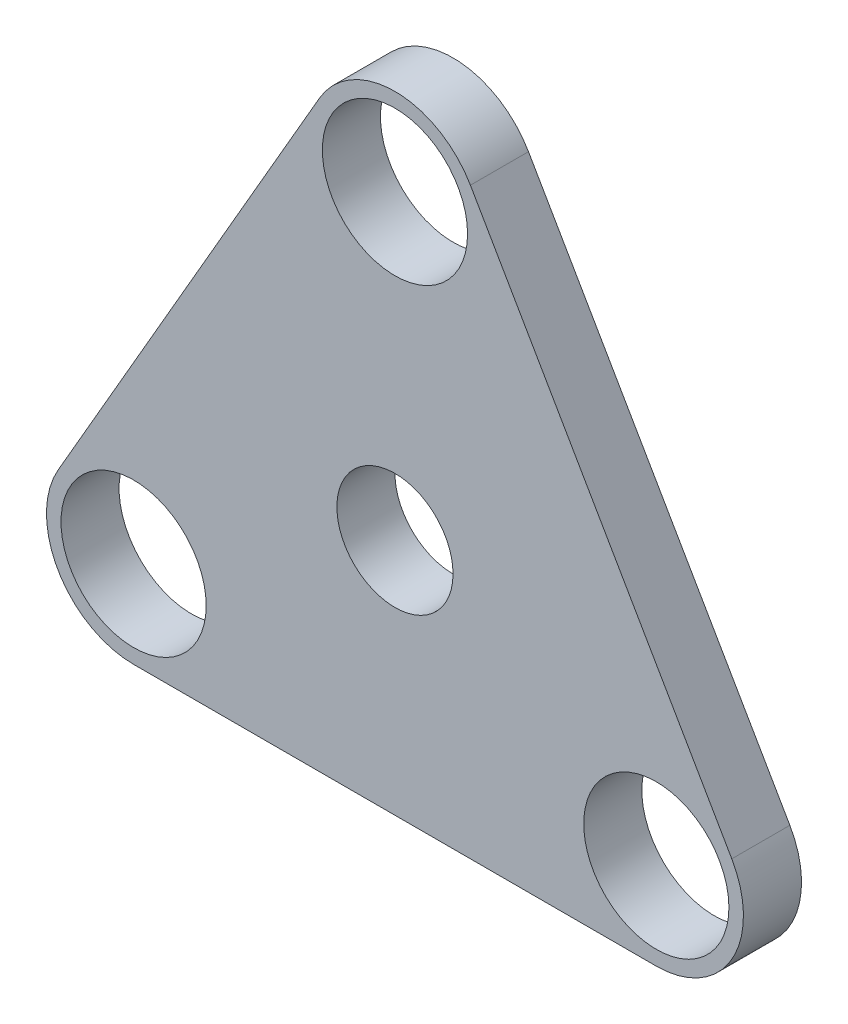
SolidWorks part; units mm, degrees
material "AISI 1020"
ref_plane "Front Plane" through (0, 0, 0) normal (0, 0, 1) x (1, 0, 0)
ref_plane "Top Plane" through (0, 0, 0) normal (0, 1, 0) x (1, 0, 0)
ref_plane "Right Plane" through (0, 0, 0) normal (1, 0, 0) x (0, 0, -1)
sketch "Sketch1" plane through (0, 0, 0) normal (0, 0, 1) x (1, 0, 0)
  line L0 (0, 13.5863) -> (0, -12.6778) construction
  line L1 (-28.575, -16.4978) -> (28.575, -16.4978) construction
  line L2 (-28.575, -16.4978) -> (0, 32.9956) construction
  line L3 (0, 32.9956) -> (28.575, -16.4978) construction
  line L4 (-9.2855, 0) -> (9.7088, 0) construction
  line L5 (14.2875, 8.2489) -> (-28.575, -16.4978) construction
  line L6 (-14.2875, 8.2489) -> (28.575, -16.4978) construction
  line L7 (-8.2489, 37.7581) -> (-36.8239, -11.7353)
  line L8 (-28.575, -26.0228) -> (28.575, -26.0228)
  line L9 (36.8239, -11.7353) -> (8.2489, 37.7581)
  circle A0 centre (0, 0) radius 6.35
  arc A1 (8.2489, 37.7581) -> (-8.2489, 37.7581) centre (0, 32.9956) ccw
  arc A2 (-36.8239, -11.7353) -> (-28.575, -26.0228) centre (-28.575, -16.4978) ccw
  arc A3 (28.575, -26.0228) -> (36.8239, -11.7353) centre (28.575, -16.4978) ccw
  circle A4 centre (-28.575, -16.4978) radius 7.9375
  circle A5 centre (0, 32.9956) radius 7.9375
  circle A6 centre (28.575, -16.4978) radius 7.9375
  point P12 (0, 0)
  dimension "D1" = 12.7
  dimension "D3" = 19.05
  dimension "D4" = 15.875
  dimension "D2" = 57.15
extrude "Boss-Extrude1" add sketch "Sketch1" along normal blind 6.35
